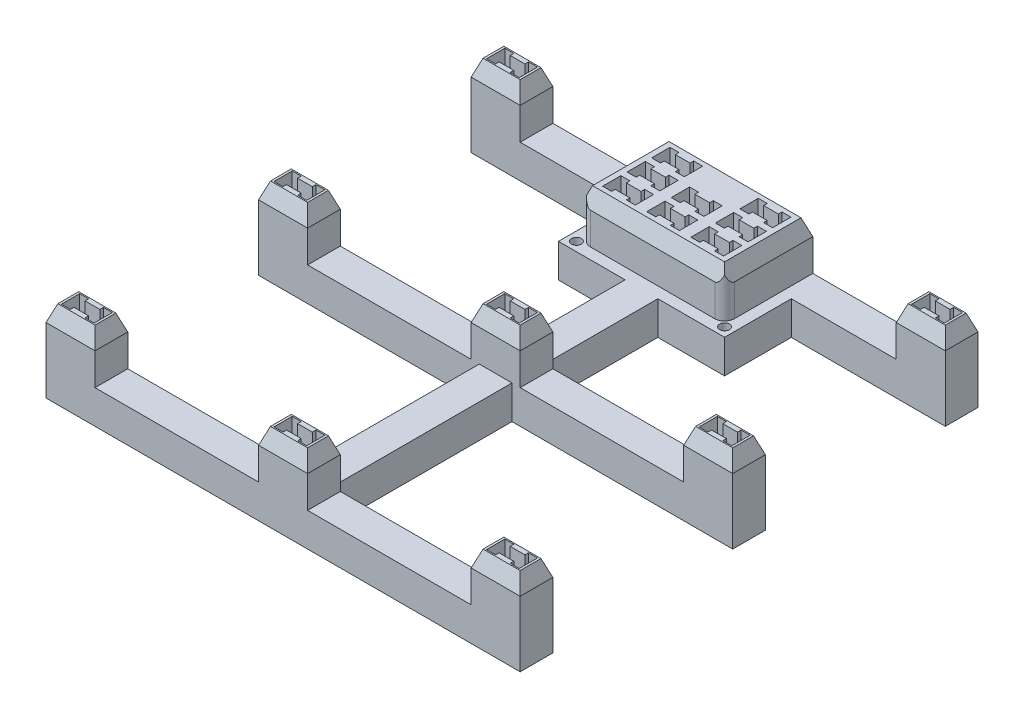
SolidWorks part; units mm, degrees
ref_plane "Front Plane" through (0, 0, 0) normal (0, 0, 1) x (1, 0, 0)
ref_plane "Top Plane" through (0, 0, 0) normal (0, 1, 0) x (1, 0, 0)
ref_plane "Right Plane" through (0, 0, 0) normal (1, 0, 0) x (0, 0, -1)
sketch "Sketch1" plane through (0, 0, 0) normal (0, 1, 0) x (1, 0, 0)
  line L0 (50.5, 130) -> (0, 130)
  line L1 (0, 140) -> (0, 130)
  line L2 (0, 140) -> (145, 140)
  line L4 (145, 130) -> (145, 140)
  line L5 (94.5, 130) -> (145, 130)
  line L6 (50.5, 130) -> (50.5, 113)
  line L7 (50.5, 113) -> (67.5, 113)
  line L8 (94.5, 113) -> (94.5, 130)
  line L9 (77.5, 113) -> (94.5, 113)
  line L10 (67.5, 113) -> (67.5, 75)
  line L11 (77.5, 75) -> (77.5, 113)
  line L12 (67.5, 75) -> (0, 75)
  line L13 (0, 65) -> (0, 75)
  line L14 (0, 65) -> (67.5, 65)
  line L15 (145, 75) -> (77.5, 75)
  line L16 (145, 65) -> (145, 75)
  line L17 (77.5, 65) -> (145, 65)
  line L18 (67.5, 65) -> (67.5, 10)
  line L19 (77.5, 10) -> (77.5, 65)
  line L20 (67.5, 10) -> (0, 10)
  line L21 (0, 10) -> (0, 0)
  line L22 (0, 0) -> (145, 0)
  line L24 (77.5, 10) -> (145, 10)
  line L25 (145, 10) -> (145, 0)
  dimension "D1" = 10
  dimension "D2" = 145
  dimension "D3" = 50.5
  dimension "D4" = 17
  dimension "D5" = 17
  dimension "D6" = 55
  dimension "D7" = 55
extrude "Boss-Extrude1" add sketch "Sketch1" along normal blind 10
sketch "Sketch2" plane through (0, 10, 0) normal (0, 1, 0) x (1, 0, 0)
  line L0 (145, 10) -> (77.5, 10) construction
  line L1 (145, 0) -> (130, 0)
  line L2 (145, 0) -> (145, 10)
  line L3 (145, 10) -> (130, 10)
  line L4 (130, 0) -> (130, 10)
  line L6 (80, 0) -> (65, 0)
  line L7 (80, 0) -> (80, 10)
  line L8 (80, 10) -> (65, 10)
  line L9 (65, 0) -> (65, 10)
  line L10 (67.5, 10) -> (0, 10) construction
  line L11 (0, 0) -> (15, 0)
  line L12 (0, 0) -> (0, 10)
  line L13 (0, 10) -> (15, 10)
  line L14 (15, 0) -> (15, 10)
  line L15 (67.5, 75) -> (0, 75) construction
  line L16 (0, 65) -> (15, 65)
  line L17 (0, 65) -> (0, 75)
  line L18 (0, 75) -> (15, 75)
  line L19 (15, 65) -> (15, 75)
  line L20 (145, 75) -> (77.5, 75) construction
  line L21 (145, 65) -> (130, 65)
  line L22 (145, 65) -> (145, 75)
  line L23 (145, 75) -> (130, 75)
  line L24 (130, 65) -> (130, 75)
  line L25 (77.5, 65) -> (145, 65) construction
  line L26 (80, 65) -> (65, 65)
  line L27 (80, 65) -> (80, 75)
  line L28 (80, 75) -> (65, 75)
  line L29 (65, 65) -> (65, 75)
  line L30 (145, 140) -> (0, 140) construction
  line L31 (145, 130) -> (130, 130)
  line L32 (145, 130) -> (145, 140)
  line L33 (145, 140) -> (130, 140)
  line L34 (130, 130) -> (130, 140)
  line L35 (0, 0) -> (145, 0) construction
  line L36 (0, 130) -> (15, 130)
  line L37 (0, 130) -> (0, 140)
  line L38 (0, 140) -> (15, 140)
  line L39 (15, 130) -> (15, 140)
  line L40 (50.5, 140) -> (94.5, 140)
  line L41 (50.5, 113) -> (94.5, 113)
  line L42 (50.5, 113) -> (50.5, 140)
  line L44 (94.5, 113) -> (94.5, 140)
  point P62 (72.5, 0)
  dimension "D1" = 15
extrude "Boss-Extrude2" add sketch "Sketch2" along normal blind 10
sketch "Sketch3" plane through (0, 20, 0) normal (0, 1, 0) x (1, 0, 0)
  line L0 (0, 140) -> (0, 130) construction
  line L1 (0, 130) -> (15, 130) construction
  line L2 (15, 130) -> (15, 140) construction
  line L3 (15, 140) -> (0, 140) construction
  line L4 (145, 0) -> (145, 10)
  line L5 (145, 10) -> (130, 10)
  line L6 (130, 10) -> (130, 0)
  line L7 (130, 0) -> (145, 0)
  line L8 (145, 0) -> (145, 10)
  line L9 (145, 10) -> (130, 10)
  line L10 (130, 10) -> (130, 0)
  line L11 (130, 0) -> (145, 0)
  line L12 (145, 130) -> (145, 140) construction
  line L13 (145, 140) -> (130, 140) construction
  line L14 (130, 140) -> (130, 130) construction
  line L15 (130, 130) -> (145, 130) construction
  line L16 (145, 65) -> (145, 75) construction
  line L17 (145, 75) -> (130, 75) construction
  line L18 (130, 75) -> (130, 65) construction
  line L19 (130, 65) -> (145, 65) construction
  line L20 (80, 65) -> (80, 75) construction
  line L21 (80, 75) -> (65, 75) construction
  line L22 (65, 75) -> (65, 65) construction
  line L23 (65, 65) -> (80, 65) construction
  line L24 (0, 75) -> (0, 65) construction
  line L25 (0, 65) -> (15, 65) construction
  line L26 (15, 65) -> (15, 75) construction
  line L27 (15, 75) -> (0, 75) construction
  line L28 (0, 10) -> (0, 0) construction
  line L29 (0, 0) -> (15, 0) construction
  line L30 (15, 0) -> (15, 10) construction
  line L31 (15, 10) -> (0, 10) construction
  line L32 (80, 0) -> (80, 10) construction
  line L33 (80, 10) -> (65, 10) construction
  line L34 (65, 10) -> (65, 0) construction
  line L35 (65, 0) -> (80, 0) construction
  line L36 (0, 140) -> (0, 130)
  line L37 (0, 130) -> (15, 130)
  line L38 (15, 130) -> (15, 140)
  line L39 (15, 140) -> (0, 140)
  line L40 (145, 130) -> (145, 140)
  line L41 (145, 140) -> (130, 140)
  line L42 (130, 140) -> (130, 130)
  line L43 (130, 130) -> (145, 130)
  line L44 (145, 65) -> (145, 75)
  line L45 (145, 75) -> (130, 75)
  line L46 (130, 75) -> (130, 65)
  line L47 (130, 65) -> (145, 65)
  line L48 (80, 65) -> (80, 75)
  line L49 (80, 75) -> (65, 75)
  line L50 (65, 75) -> (65, 65)
  line L51 (65, 65) -> (80, 65)
  line L52 (0, 75) -> (0, 65)
  line L53 (0, 65) -> (15, 65)
  line L54 (15, 65) -> (15, 75)
  line L55 (15, 75) -> (0, 75)
  line L56 (0, 10) -> (0, 0)
  line L57 (0, 0) -> (15, 0)
  line L58 (15, 0) -> (15, 10)
  line L59 (15, 10) -> (0, 10)
  line L60 (80, 0) -> (80, 10)
  line L61 (80, 10) -> (65, 10)
  line L62 (65, 10) -> (65, 0)
  line L63 (65, 0) -> (80, 0)
  line L68 (50.5, 140) -> (50.5, 113)
  line L69 (50.5, 113) -> (94.5, 113)
  line L70 (94.5, 113) -> (94.5, 140)
  line L71 (94.5, 140) -> (50.5, 140)
  line L72 (50.5, 140) -> (50.5, 113)
  line L73 (50.5, 113) -> (94.5, 113)
  line L74 (94.5, 113) -> (94.5, 140)
  line L75 (94.5, 140) -> (50.5, 140)
  dimension "D1" = 0
  dimension "D2" = 0
extrude "Boss-Extrude3" add sketch "Sketch3" along normal blind 5 draft 20
sketch "Sketch4" plane through (0, 25, 0) normal (0, 1, 0) x (1, 0, 0)
  line L0 (94.5, 140) -> (50.5, 140) construction
  line L1 (89, 140) -> (56, 140)
  line L2 (89, 140) -> (89, 138.1801)
  line L3 (89, 138.1801) -> (56, 138.1801)
  line L4 (56, 140) -> (56, 138.1801)
  line L5 (92.6802, 138.1801) -> (52.3199, 138.1801) construction
  point P9 (72.5, 140)
  dimension "D1" = 33
extrude "Cut-Extrude1" cut sketch "Sketch4" against normal blind 15
sketch "Sketch5" plane through (0, 25, 0) normal (0, 1, 0) x (1, 0, 0)
  line L1 (142.5, 3.3) -> (132.5, 3.3)
  line L2 (142.5, 3.3) -> (142.5, 6.7)
  line L3 (142.5, 6.7) -> (132.5, 6.7)
  line L4 (132.5, 3.3) -> (132.5, 6.7)
  line L6 (132.5, 5) -> (131.8199, 5) construction
  line L7 (131.8199, 8.1802) -> (131.8199, 1.8199) construction
  line L8 (137.5, 6.7) -> (137.5, 8.1802) construction
  line L9 (143.1802, 8.1802) -> (131.8199, 8.1802) construction
  dimension "D1" = 3.4
  dimension "D2" = 10
extrude "Cut-Extrude2" cut sketch "Sketch5" against normal blind 7.75
sketch "Sketch7" plane through (0, 25, 0) normal (0, 1, 0) x (1, 0, 0)
  line L0 (142.5, 6.7) -> (132.5, 6.7) construction
  line L1 (132.5, 6.7) -> (135.25, 6.7)
  line L2 (132.5, 6.7) -> (132.5, 7.8)
  line L3 (132.5, 7.8) -> (135.25, 7.8)
  line L4 (135.25, 6.7) -> (135.25, 7.8)
  line L5 (132.5, 6.7) -> (132.5, 3.3) construction
  line L6 (132.5, 6.7) -> (132.5, 3.3) construction
  line L8 (132.5, 3.3) -> (135.25, 3.3)
  line L9 (132.5, 3.3) -> (132.5, 2.2)
  line L10 (132.5, 2.2) -> (135.25, 2.2)
  line L11 (135.25, 3.3) -> (135.25, 2.2)
  line L12 (142.5, 6.7) -> (139.75, 6.7)
  line L13 (142.5, 6.7) -> (142.5, 7.8)
  line L14 (142.5, 7.8) -> (139.75, 7.8)
  line L15 (139.75, 6.7) -> (139.75, 7.8)
  line L16 (142.5, 3.3) -> (139.75, 3.3)
  line L17 (142.5, 3.3) -> (142.5, 2.2)
  line L18 (142.5, 2.2) -> (139.75, 2.2)
  line L19 (139.75, 3.3) -> (139.75, 2.2)
  dimension "D1" = 2.75
  dimension "D2" = 1.1
extrude "Cut-Extrude4" cut sketch "Sketch7" against normal up to surface (7.75 mm away) up to face at (137.5, 17.25, -5)
pattern_linear "LPattern1" count 3 spacing 65 along (-1, 0, 0) count 3 spacing 65 along (0, 0, -1) skipping (1, 2) of "Cut-Extrude2", "Cut-Extrude4"
sketch "Sketch6" plane through (0, 25, 0) normal (0, 1, 0) x (1, 0, 0)
  line L21 (91, 117.3) -> (81, 117.3)
  line L22 (91, 117.3) -> (91, 120.7)
  line L23 (91, 120.7) -> (81, 120.7)
  line L36 (81, 117.3) -> (81, 120.7)
  line L37 (67.5, 117.3) -> (67.5, 120.7)
  line L39 (77.5, 117.3) -> (67.5, 117.3)
  line L68 (50.5, 113) -> (94.5, 113) construction
  line L69 (94.5, 113) -> (94.5, 140) construction
  line L70 (77.5, 120.7) -> (67.5, 120.7)
  line L71 (77.5, 117.3) -> (77.5, 120.7)
  line L72 (54, 117.3) -> (54, 120.7)
  line L73 (64, 117.3) -> (54, 117.3)
  line L74 (64, 120.7) -> (54, 120.7)
  line L75 (64, 117.3) -> (64, 120.7)
  line L76 (67.5, 124.8) -> (67.5, 128.2)
  line L77 (77.5, 124.8) -> (67.5, 124.8)
  line L78 (77.5, 128.2) -> (67.5, 128.2)
  line L79 (77.5, 124.8) -> (77.5, 128.2)
  line L80 (54, 124.8) -> (54, 128.2)
  line L81 (64, 124.8) -> (54, 124.8)
  line L82 (64, 128.2) -> (54, 128.2)
  line L83 (64, 124.8) -> (64, 128.2)
  line L84 (67.5, 132.3) -> (67.5, 135.7) [skipped]
  line L85 (77.5, 132.3) -> (67.5, 132.3) [skipped]
  line L86 (77.5, 135.7) -> (67.5, 135.7) [skipped]
  line L87 (77.5, 132.3) -> (77.5, 135.7) [skipped]
  line L88 (54, 132.3) -> (54, 135.7)
  line L89 (64, 132.3) -> (54, 132.3)
  line L90 (64, 135.7) -> (54, 135.7)
  line L91 (64, 132.3) -> (64, 135.7)
  line L92 (81, 124.8) -> (81, 128.2)
  line L93 (91, 124.8) -> (81, 124.8)
  line L94 (91, 128.2) -> (81, 128.2)
  line L95 (91, 124.8) -> (91, 128.2)
  line L96 (81, 132.3) -> (81, 135.7)
  line L97 (91, 132.3) -> (81, 132.3)
  line L98 (91, 135.7) -> (81, 135.7)
  line L99 (91, 132.3) -> (91, 135.7)
  point P40 (91, 119)
  point P45 (86, 117.3)
  dimension "D1" = 10
  dimension "D2" = 3.4
  dimension "D3" = 6
  dimension "D4" = 8.5
  dimension "D5" = 3
  dimension "D6" = 3
extrude "Cut-Extrude3" cut sketch "Sketch6" against normal blind 7.75
fillet "Fillet1" radius 3 2 edges at (50.5, 10, -113) (94.5, 10, -113)
sketch "Sketch9" plane through (0, 25, 0) normal (0, 1, 0) x (1, 0, 0)
  line L0 (81, 120.7) -> (83.75, 120.7)
  line L1 (81, 120.7) -> (81, 121.8)
  line L2 (81, 121.8) -> (83.75, 121.8)
  line L3 (83.75, 120.7) -> (83.75, 121.8)
  line L4 (81, 117.3) -> (83.75, 117.3)
  line L5 (81, 117.3) -> (81, 116.2)
  line L6 (81, 116.2) -> (83.75, 116.2)
  line L7 (83.75, 117.3) -> (83.75, 116.2)
  line L8 (91, 120.7) -> (88.25, 120.7)
  line L9 (91, 120.7) -> (91, 121.8)
  line L10 (91, 121.8) -> (88.25, 121.8)
  line L11 (88.25, 120.7) -> (88.25, 121.8)
  line L12 (91, 117.3) -> (88.25, 117.3)
  line L13 (91, 117.3) -> (91, 116.2)
  line L14 (91, 116.2) -> (88.25, 116.2)
  line L15 (88.25, 117.3) -> (88.25, 116.2)
  line L16 (81, 120.7) -> (81, 117.3) construction
  line L17 (81, 117.3) -> (91, 117.3) construction
  line L18 (91, 120.7) -> (81, 120.7) construction
  dimension "D1" = 2.75
  dimension "D2" = 1.1
extrude "Cut-Extrude5" cut sketch "Sketch9" against normal up to surface (7.75 mm away) up to face at (86, 17.25, -119)
pattern_linear "LPattern2" count 3 spacing 13.5 along (-1, 0, 0) count 3 spacing 7.5 along (0, 0, -1) skipping (1, 2) of "Cut-Extrude5"
sketch "Sketch10" plane through (0, 10, 0) normal (0, 1, 0) x (1, 0, 0)
  line L0 (50.5, 130) -> (47.1, 130)
  line L1 (15, 130) -> (50.5, 130) construction
  line L2 (47.1, 130) -> (47.1, 109.6)
  line L3 (47.1, 109.6) -> (67.5, 109.6)
  line L4 (67.5, 113) -> (67.5, 75) construction
  line L5 (67.5, 109.6) -> (67.5, 113)
  line L6 (77.5, 113) -> (77.5, 109.6)
  line L7 (77.5, 75) -> (77.5, 113) construction
  line L8 (77.5, 109.6) -> (97.9, 109.6)
  line L9 (97.9, 109.6) -> (97.9, 130)
  line L10 (94.5, 130) -> (130, 130) construction
  line L11 (97.9, 130) -> (94.5, 130)
  line L12 (94.5, 116) -> (94.5, 140) construction
  line L13 (53.5, 113) -> (91.5, 113) construction
  line L14 (50.5, 140) -> (50.5, 116) construction
  line L15 (94.5, 116) -> (94.5, 130)
  line L16 (53.5, 113) -> (67.5, 113)
  line L17 (50.5, 130) -> (50.5, 116)
  line L18 (77.5, 113) -> (91.5, 113)
  arc A0 (93.6213, 113.8787) -> (94.5, 116) centre (91.5, 116) ccw construction
  arc A1 (91.5, 113) -> (93.6213, 113.8787) centre (91.5, 116) ccw construction
  arc A2 (51.3787, 113.8787) -> (53.5, 113) centre (53.5, 116) ccw construction
  arc A3 (50.5, 116) -> (51.3787, 113.8787) centre (53.5, 116) ccw construction
  arc A4 (93.6213, 113.8787) -> (94.5, 116) centre (91.5, 116) ccw
  arc A5 (91.5, 113) -> (93.6213, 113.8787) centre (91.5, 116) ccw
  arc A6 (51.3787, 113.8787) -> (53.5, 113) centre (53.5, 116) ccw
  arc A7 (50.5, 116) -> (51.3787, 113.8787) centre (53.5, 116) ccw
  dimension "D1" = 3.4
extrude "Boss-Extrude4" add sketch "Sketch10" against normal up to surface (10 mm away) up to face at (72.5, 0, -80.106)
sketch "Sketch11" plane through (0, 0, 0) normal (0, -1, 0) x (1, 0, 0)
  line L0 (95.1511, -112.3491) -> (49.8489, -112.3491) construction
  line L1 (97.9, -130) -> (97.9, -109.6) construction
  line L2 (97.9, -109.6) -> (77.5, -109.6) construction
  line L3 (47.1, -109.6) -> (47.1, -130) construction
  circle A0 centre (95.1511, -112.3491) radius 1.5
  circle A1 centre (49.8489, -112.3491) radius 1.5
  point P8 (51.0425, -112.4091)
  dimension "D1" = 3
  dimension "D2" = 2.7489
  dimension "D3" = 2.7491
  dimension "D4" = 2.7489
extrude "Cut-Extrude6" cut sketch "Sketch11" against normal up to next
other "Move Face1" face at (105, 10, -5) face at (40, 10, -5) face at (72.5, 10, -37.5) face at (105, 10, -70) face at (40, 10, -70) face at (95.1511, 10, -110.8491) offset 0.25 parameters "D1"=0.25
